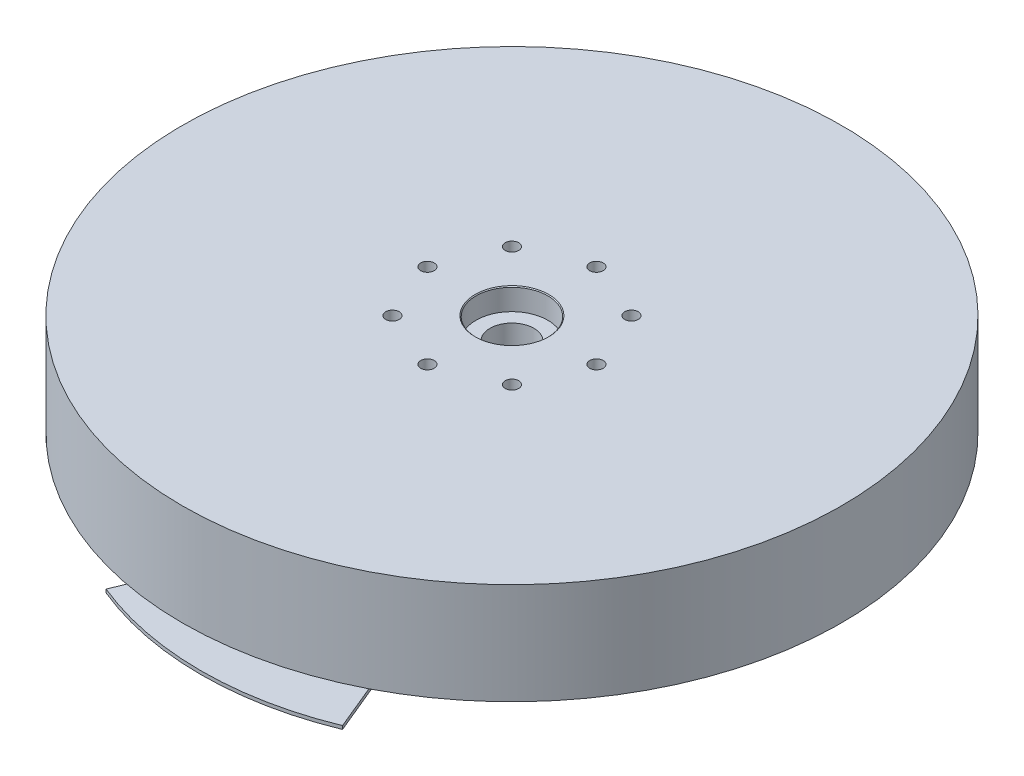
SolidWorks part; units mm, degrees
material "Ст 3 ГОСТ 380-88"
ref_plane "Front Plane" through (0, 0, 0) normal (0, 0, 1) x (1, 0, 0)
ref_plane "Top Plane" through (0, 0, 0) normal (0, 1, 0) x (1, 0, 0)
ref_plane "Right Plane" through (0, 0, 0) normal (1, 0, 0) x (0, 0, -1)
sketch "Sketch1" plane through (0, 0, 0) normal (1, 0, 0) x (0, 0, -1)
  line L0 (0, -14) -> (0, -31.7786) construction
  line L1 (-195, 60) -> (-195, 0)
  line L2 (-195, 0) -> (-185.5, 0)
  line L3 (-74.5, 0) -> (-74.5, -14)
  line L4 (-74.5, -14) -> (-15.5, -14)
  line L5 (-195, 60) -> (-185.5, 60)
  line L6 (0, 30.6711) -> (0, 60) construction
  line L7 (-13, 47) -> (-13, -11.5)
  line L8 (-13, -14) -> (0, -14) construction
  line L9 (0, 30.6711) -> (0, -14) construction
  line L10 (0, -14) -> (0, 30.6711) construction
  line L11 (-13, 60) -> (0, 60) construction
  line L12 (-15.5, 60) -> (-13, 57.5) construction
  line L13 (-15.5, -14) -> (-13, -11.5)
  line L14 (-21.25, 59.5) -> (-21.25, 47)
  line L15 (-21.25, 47) -> (-13, 47)
  line L16 (-21.25, 60) -> (-15.5, 60) construction
  line L17 (-13, 57.5) -> (-13, 47) construction
  line L18 (-21.75, 60) -> (-21.25, 59.5)
  line L19 (-185.5, 0) -> (-185.5, 10)
  line L20 (-185.5, 10) -> (-74.5, 10)
  line L21 (-74.5, 0) -> (-74.5, 10)
  line L22 (-185.5, 0) -> (-74.5, 0) construction
  line L23 (-185.5, 60) -> (-185.5, 50) construction
  line L24 (-185.5, 50) -> (-74.5, 50) construction
  line L25 (-74.5, 50) -> (-74.5, 60) construction
  line L26 (-185.5, 60) -> (-74.5, 60) construction
  line L27 (-74.5, 60) -> (-21.75, 60)
  line L28 (-185.5, 60) -> (-74.5, 60)
  dimension "D1" = 60
  dimension "D2" = 390
  dimension "D3" = 149
  dimension "D4" = 14
  dimension "D5" = 13
  dimension "D6" = 13
  dimension "D7" = 42.5
  dimension "D10" = 10
  dimension "D11" = 9.5
  dimension "D13" = 10
revolve "Revolve1" add sketch "Sketch1" angle 360 about L0
sketch "Sketch2" plane through (0, 60, 0) normal (0, 1, 0) x (1, 0, 0)
  line L0 (-50, 0) -> (0, 0) construction
  circle A0 centre (-50, 0) radius 4
  circle A1 centre (-35.3553, 35.3553) radius 4
  circle A2 centre (0, 50) radius 4
  circle A3 centre (35.3553, 35.3553) radius 4
  circle A4 centre (50, 0) radius 4
  circle A5 centre (35.3553, -35.3553) radius 4
  circle A6 centre (0, -50) radius 4
  circle A7 centre (-35.3553, -35.3553) radius 4
  point P21 (0, 0)
  dimension "D1" = 8
  dimension "D2" = 8
  dimension "D3" = 50
extrude "Cut-Extrude1" cut sketch "Sketch2" against normal through all both and the other way through all
sketch "Sketch3" plane through (0, 10, 0) normal (0, -1, 0) x (1, 0, 0)
  line L0 (0, 129.2853) -> (0, -136.9499) construction
  line L1 (0, 0) -> (0, 132.1781) construction
  line L2 (0, 0) -> (-104.479, 104.479) construction
  circle A0 centre (0, 82) radius 2
  circle A1 centre (0, 120) radius 2
  circle A2 centre (84.8528, 84.8528) radius 2
  circle A3 centre (57.9828, 57.9828) radius 2 construction
  circle A4 centre (120, 0) radius 2
  circle A5 centre (82, 0) radius 2
  circle A6 centre (84.8528, -84.8528) radius 2
  circle A7 centre (57.9828, -57.9828) radius 2 construction
  circle A8 centre (0, -120) radius 2
  circle A9 centre (0, -82) radius 2
  circle A10 centre (-84.8528, -84.8528) radius 2
  circle A11 centre (-57.9828, -57.9828) radius 2 construction
  circle A12 centre (-120, 0) radius 2
  circle A13 centre (-82, 0) radius 2
  circle A14 centre (-84.8528, 84.8528) radius 2
  circle A15 centre (-57.9828, 57.9828) radius 2 construction
  circle A16 centre (0, 0) radius 120 construction
  point P104 (0, 0)
  dimension "D1" = 4
  dimension "D4" = 120
  dimension "D3" = 240
  dimension "D2" = 82
  dimension "D6" = 45
  dimension "D5" = 8
extrude "Cut-Extrude2" [suppressed] cut sketch "Sketch3" against normal blind 15
ref_plane "Plane1" through (0, 30, 0) normal (0, -1, 0) x (-1, 0, 0)
mirror "Mirror1" [suppressed] about plane through (0, 30, 0) normal (0, -1, 0)
sketch "Sketch4" plane through (0, 60, 0) normal (0, 1, 0) x (1, 0, 0)
  circle A0 centre (0, 50) radius 8
  circle A1 centre (0, 0) radius 50 construction
  circle A2 centre (35.3553, 35.3553) radius 8
  circle A3 centre (50, 0) radius 8
  circle A4 centre (35.3553, -35.3553) radius 8
  circle A5 centre (0, -50) radius 8
  circle A6 centre (-35.3553, -35.3553) radius 8
  circle A7 centre (-50, 0) radius 8
  circle A8 centre (-35.3553, 35.3553) radius 8
  point P22 (0, 0)
  dimension "D1" = 16
  dimension "D2" = 8
extrude "Cut-Extrude3" [suppressed] cut sketch "Sketch4" against normal blind 12
sketch "Sketch5" plane through (0, -14, 0) normal (0, -1, 0) x (1, 0, 0)
  circle A0 centre (35.3553, -35.3553) radius 4 construction
  circle A1 centre (0, 0) radius 74.5
  circle A2 centre (0, 0) radius 74.5
  circle A3 centre (0, -50) radius 4 construction
  circle A4 centre (-35.3553, -35.3553) radius 4 construction
  circle A5 centre (-50, 0) radius 4 construction
  circle A6 centre (50, 0) radius 4 construction
  circle A7 centre (35.3553, 35.3553) radius 4 construction
  circle A8 centre (-35.3553, 35.3553) radius 4 construction
  circle A9 centre (0, 50) radius 4 construction
  circle A10 centre (35.3553, -35.3553) radius 4
  circle A11 centre (0, -50) radius 4
  circle A12 centre (-35.3553, -35.3553) radius 4
  circle A13 centre (-50, 0) radius 4
  circle A14 centre (50, 0) radius 4
  circle A15 centre (35.3553, 35.3553) radius 4
  circle A16 centre (-35.3553, 35.3553) radius 4
  circle A17 centre (0, 50) radius 4
  circle A18 centre (0, 0) radius 13 construction
  circle A19 centre (0, 0) radius 13
  dimension "D1" = 0
extrude "Boss-Extrude1" add sketch "Sketch5" along normal blind 1 from offset 30 separate body
sketch "Sketch6" plane through (0, -14, 0) normal (0, -1, 0) x (1, 0, 0)
  circle A1 centre (0, 0) radius 74.5
  circle A2 centre (0, 0) radius 74.5
  dimension "D1" = 0
extrude "Cut-Extrude4" cut sketch "Sketch6" against normal blind 2.5
chamfer "Chamfer1" [suppressed] distance 5 angle 60
chamfer "Chamfer2" [suppressed] distance 10 angle 30
sketch "Sketch7" plane through (0, 10, 0) normal (0, -1, 0) x (1, 0, 0)
  line L0 (0, 234.4435) -> (0, -294.1465) construction
  line L1 (0, 0) -> (28.7013, 69.291) construction
  line L3 (-28.7013, 69.291) -> (-70.4138, 169.9938) construction
  line L4 (28.2387, 69.4808) -> (69.9516, 170.1845)
  line L5 (-28.2387, 69.4808) -> (-69.9516, 170.1845)
  line L6 (28.7013, 69.291) -> (70.4138, 169.9938) construction
  line L7 (70.9878, 171.3797) -> (89.9519, 217.1632) construction
  line L8 (70.4138, 169.9938) -> (70.9878, 171.3797) construction
  line L9 (0, 75) -> (22.6048, 75) construction
  line L10 (0, 129.5) -> (22.6048, 129.5) construction
  line L11 (0, 184) -> (132.4756, 184) construction
  circle A1 centre (0, 0) radius 13 construction
  arc A2 (69.9516, 170.1845) -> (-69.9516, 170.1845) centre (0, 0) ccw
  circle A3 centre (0, 157) radius 2.6
  circle A4 centre (0, 0) radius 185.5 construction
  circle A6 centre (0, 102) radius 2.6
  arc A8 (-69.9516, 170.1845) -> (-70.4138, 169.9938) centre (0, 0) ccw construction
  arc A9 (28.2387, 69.4808) -> (-28.2387, 69.4808) centre (0, 0) ccw
  dimension "D1" = 22.5
  dimension "D2" = 184
  dimension "D3" = 371
  dimension "D5" = 0.5
  dimension "D6" = 75
  dimension "D7" = 5.2
  dimension "D4" = 109
  dimension "D8" = 54.5
  dimension "D9" = 55
extrude "Boss-Extrude3" add sketch "Sketch7" along normal blind 5 from offset 0.01 separate body
sketch "Sketch8" plane through (0, 4.99, 0) normal (0, -1, 0) x (1, 0, 0)
  line L2 (28.2387, 69.4808) -> (69.9516, 170.1845)
  line L3 (-69.9516, 170.1845) -> (-28.2387, 69.4808)
  line L4 (28.2387, 69.4808) -> (69.9516, 170.1845)
  line L5 (-69.9516, 170.1845) -> (-28.2387, 69.4808)
  circle A0 centre (0, 102) radius 2.6 construction
  circle A1 centre (0, 157) radius 2.6 construction
  arc A2 (28.2387, 69.4808) -> (-28.2387, 69.4808) centre (0, 0) ccw
  arc A3 (69.9516, 170.1845) -> (-69.9516, 170.1845) centre (0, 0) ccw
  arc A4 (28.2387, 69.4808) -> (-28.2387, 69.4808) centre (0, 0) ccw
  arc A5 (69.9516, 170.1845) -> (-69.9516, 170.1845) centre (0, 0) ccw
  circle A6 centre (0, 102) radius 2.6
  circle A7 centre (0, 157) radius 2.6
  dimension "D1" = 0
extrude "Boss-Extrude4" add sketch "Sketch8" along normal blind 5 separate body
chamfer "Chamfer3" distance 3.5 angle 45 2 edges at (0, -0.01, 99.4) (0, -0.01, 154.4)
chamfer "Chamfer4" distance 3.5 angle 45 2 edges at (0, 9.99, 104.6) (0, 9.99, 154.4)
sketch "Sketch9" plane through (0, 10, 0) normal (0, -1, 0) x (1, 0, 0)
  line L0 (0, 0) -> (0, 213.1478) construction
  circle A0 centre (0, 157) radius 2.6
  circle A1 centre (0, 157) radius 2.6 construction
  circle A3 centre (0, 102) radius 2.6
  circle A4 centre (0, 102) radius 2.6 construction
  circle A5 centre (111.0158, 111.0158) radius 2.6
  circle A6 centre (72.1249, 72.1249) radius 2.6
  circle A7 centre (157, 0) radius 2.6
  circle A8 centre (102, 0) radius 2.6
  circle A9 centre (111.0158, -111.0158) radius 2.6
  circle A10 centre (72.1249, -72.1249) radius 2.6
  circle A11 centre (0, -157) radius 2.6
  circle A12 centre (0, -102) radius 2.6
  circle A13 centre (-111.0158, -111.0158) radius 2.6
  circle A14 centre (-72.1249, -72.1249) radius 2.6
  circle A15 centre (-157, 0) radius 2.6
  circle A16 centre (-102, 0) radius 2.6
  circle A17 centre (-111.0158, 111.0158) radius 2.6
  circle A18 centre (-72.1249, 72.1249) radius 2.6
  point P42 (0, 0)
  dimension "D1" = 5.2
  dimension "D2" = 8
extrude "Cut-Extrude5" cut sketch "Sketch9" against normal blind 15
sketch "Sketch10" plane through (0, -0.01, 0) normal (0, -1, 0) x (1, 0, 0)
  line L0 (-30.5248, 75) -> (30.5248, 75)
  line L1 (28.2387, 69.4808) -> (69.9516, 170.1845) construction
  line L2 (30.5248, 75) -> (28.2387, 69.4808)
  line L3 (28.2387, 69.4808) -> (-28.2387, 69.4808)
  line L4 (-28.2387, 69.4808) -> (-30.5248, 75)
  point P3 (0, 75)
extrude "Cut-Extrude6" cut sketch "Sketch10" against normal blind 10
pattern_circular "CirPattern5" count 4 over 360 about axis through (0, -14, 0) along (0, 1, 0) reverse direction yes of bodies 119 120
sketch "Sketch11" plane through (0, -0.01, 0) normal (0, -1, 0) x (1, 0, 0)
  line L3 (-30.5248, 75) -> (30.5248, 75)
  line L4 (30.5248, 75) -> (69.9516, 170.1845)
  line L5 (-69.9516, 170.1845) -> (-30.5248, 75)
  line L6 (-30.5248, 75) -> (30.5248, 75)
  line L7 (30.5248, 75) -> (69.9516, 170.1845)
  line L8 (-69.9516, 170.1845) -> (-30.5248, 75)
  arc A1 (69.9516, 170.1845) -> (-69.9516, 170.1845) centre (0, 0) ccw
  arc A2 (69.9516, 170.1845) -> (-69.9516, 170.1845) centre (0, 0) ccw
  dimension "D1" = 0
extrude "Boss-Extrude5" add sketch "Sketch11" along normal blind 2 from offset 30 separate body contours L6 L7 A2 L8
sketch "Sketch12" plane through (0, -11.5, 0) normal (0, -1, 0) x (1, 0, 0)
  circle A0 centre (0, 0) radius 13
  circle A1 centre (0, 0) radius 22.5
  dimension "D1" = 45
  dimension "D2" = 26
extrude "Cut-Extrude7" cut sketch "Sketch12" against normal blind 20
chamfer "Chamfer7" distance 1.5 angle 45 1 edges at (0, -11.5, -22.5)
thread "Thread2" pitch 1.5 method cut trim with start face yes trim with end face yes profile "Thread Profile3" start angle 0, offset 10, length 0, pitch 1.5, diameter 45
ref_plane "Plane4" through (22.5, -20, 0) normal (0, 0, 1) x (1, 0, 0)
sketch "Thread Profile3" plane through (22.5, -20, 0) normal (0, 0, 1) x (1, 0, 0)
  line L0 (0, 0) -> (0, 1.5) construction
  line L1 (0, 0) -> (0.8119, 0.4687)
  line L2 (0.8119, 0.4687) -> (0.8119, 0.6562)
  line L3 (0.8119, 0.6562) -> (0, 1.125)
  line L4 (0.8119, 0.5625) -> (0, 0.5625) construction
  line L11 (0, 0) -> (0, 1.125)
  point P2 (0, 0)
  dimension "Pitch" = 1.5
  dimension "Profile_Angle" = 60
  dimension "Profile_Land" = 0.1875
  dimension "Profile_Height" = 0.8119
